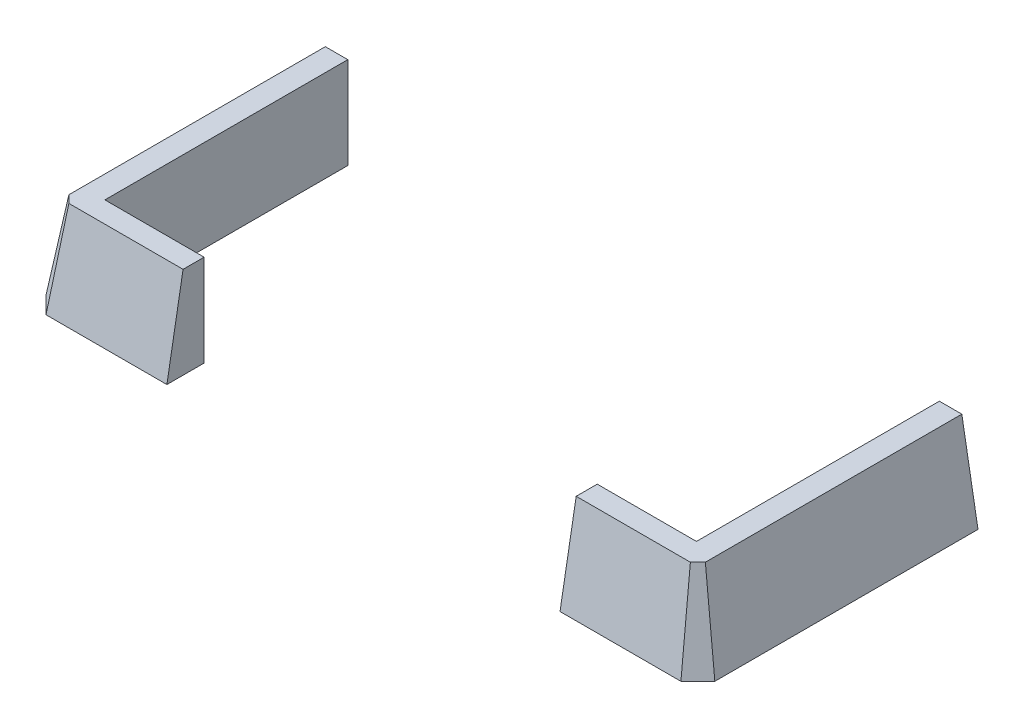
SolidWorks part; units mm, degrees
ref_plane "Front Plane" through (0, 0, 0) normal (0, 0, 1) x (1, 0, 0)
ref_plane "Top Plane" through (0, 0, 0) normal (0, 1, 0) x (1, 0, 0)
ref_plane "Right Plane" through (0, 0, 0) normal (1, 0, 0) x (0, 0, -1)
sketch "Sketch1" plane through (0, 0, 0) normal (0, 1, 0) x (1, 0, 0)
  line L9 (0, 0) -> (-158, 0) construction
  line L10 (0, 0) -> (0, 76.9384) construction
  line L11 (0, 0) -> (-158, 0) construction
  line L12 (-158, 99.7575) -> (-158, -30.0025) construction
  line L14 (-158, 99.7575) -> (-170, 99.7575) construction
  line L16 (-170, 99.7575) -> (-170, -41.2425) construction
  line L17 (-170, -41.2425) -> (-158, -41.2425) construction
  line L19 (-158, -30.0025) -> (-105, -30.0025) construction
  line L20 (-105, -30.0025) -> (-105, -41.2425) construction
  line L21 (-105, -41.2425) -> (-158, -41.2425) construction
  line L22 (-158, -30.0025) -> (-158, -41.2425) construction
  dimension "D5" = 158
  dimension "D6" = 12
  dimension "D7" = 53
  dimension "D8" = 11.24
  dimension "D9" = 41.2425
  dimension "D10" = 141
ref_plane "Plane1" through (0, -25, 0) normal (0, 1, 0) x (1, 0, 0)
ref_plane "Plane2" through (0, 24, 0) normal (0, 1, 0) x (1, 0, 0)
sketch "Sketch3" plane through (0, 24, 0) normal (0, 1, 0) x (1, 0, 0)
  line L0 (-170, 99.7575) -> (-158, 99.7575)
  line L1 (-158, 99.7575) -> (-158, -30.0025)
  line L2 (-158, -30.0025) -> (-105, -30.0025)
  line L3 (-105, -30.0025) -> (-105, -41.2425)
  line L4 (-105, -41.2425) -> (-166, -41.2425)
  line L5 (-170, -37.2425) -> (-170, 99.7575)
  line L6 (-166, -41.2425) -> (-170, -37.2425)
  point P11 (-170, -41.2425)
extrude "Boss-Extrude1" add sketch "Sketch3" against normal up to surface (49 mm away) up to plane "Plane1"
draft "Draft1" type of draft neutral plane draft angle 10 faces to draft 3 face at (-135.5, -0.5, 41.2425) face at (-168, -0.5, 39.2425) face at (-170, -0.5, -31.2575) neutral plane through (0, 24, 0) neutral plane normal (0, 1, 0) parameters "D1"=10
mirror "Mirror2" about plane through (0, 0, 0) normal (1, 0, 0) of bodies 105
